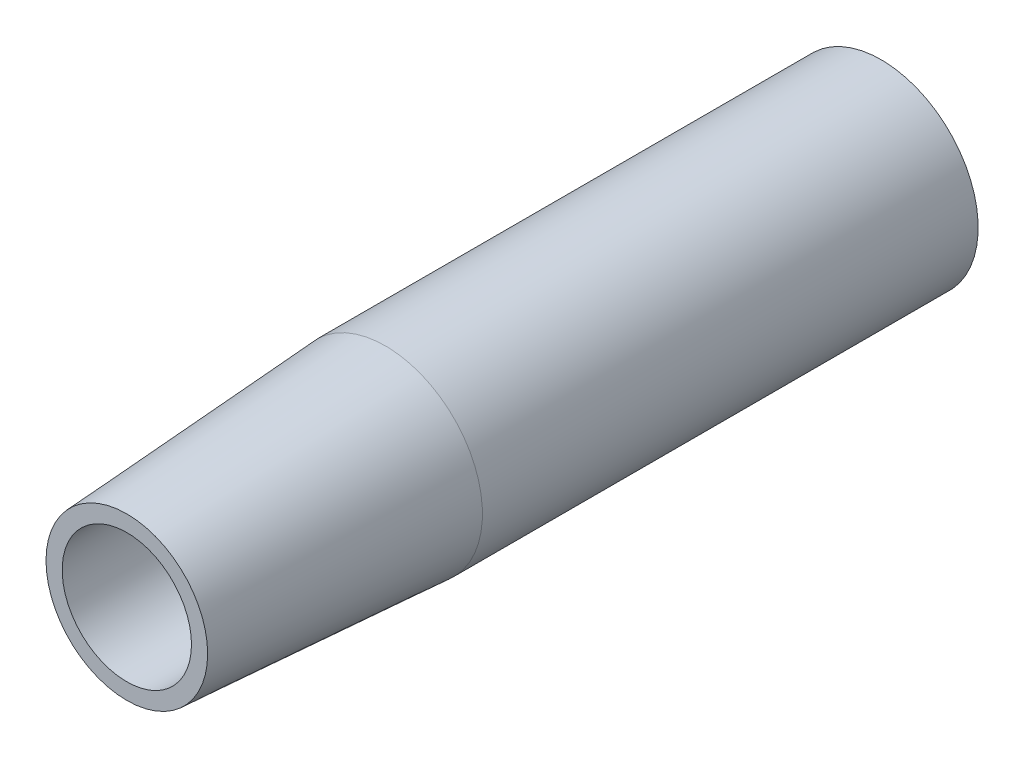
SolidWorks part; units mm, degrees
ref_plane "정면" through (0, 0, 0) normal (0, 0, 1) x (1, 0, 0)
ref_plane "윗면" through (0, 0, 0) normal (0, 1, 0) x (1, 0, 0)
ref_plane "우측면" through (0, 0, 0) normal (1, 0, 0) x (0, 0, -1)
sketch "스케치1" plane through (0, 0, 0) normal (0, 0, 1) x (1, 0, 0)
  circle A0 centre (0, 0) radius 15
  dimension "D1" = 30
extrude "보스-돌출1" add sketch "스케치1" along normal blind 77
sketch "스케치2" plane through (0, 0, 77) normal (0, 0, 1) x (1, 0, 0)
  circle A0 centre (0, 0) radius 15
ref_plane "평면1" through (0, 0, 117) normal (0, 0, 1) x (1, 0, 0)
sketch "스케치3" plane through (0, 0, 117) normal (0, 0, 1) x (1, 0, 0)
  circle A0 centre (0, 0) radius 12.5
  dimension "D1" = 25
loft "로프트1" add profiles "스케치3", "스케치2" connector at (-8.5755, -9.0945, 117) connector at (-10.5532, -10.6598, 77)
sketch "스케치5" plane through (0, 0, 117) normal (0, 0, 1) x (1, 0, 0)
  circle A0 centre (0, 0) radius 10
  dimension "D1" = 20
extrude "컷-돌출1" cut sketch "스케치5" against normal blind 60
sketch "스케치6" plane through (0, 0, 0) normal (0, 0, -1) x (-1, 0, 0)
  circle A0 centre (0, 0) radius 10
  dimension "D1" = 20
extrude "컷-돌출2" cut sketch "스케치6" against normal blind 40.5
chamfer "모따기1" distance 3.5 angle 60 1 edges at (-10, 0, 0) first distance on face at (-10, 0, 0)
chamfer "모따기2" distance 1 angle 45 1 edges at (13.5, 0, 0) first distance on face at (13.5, 0, 0)
